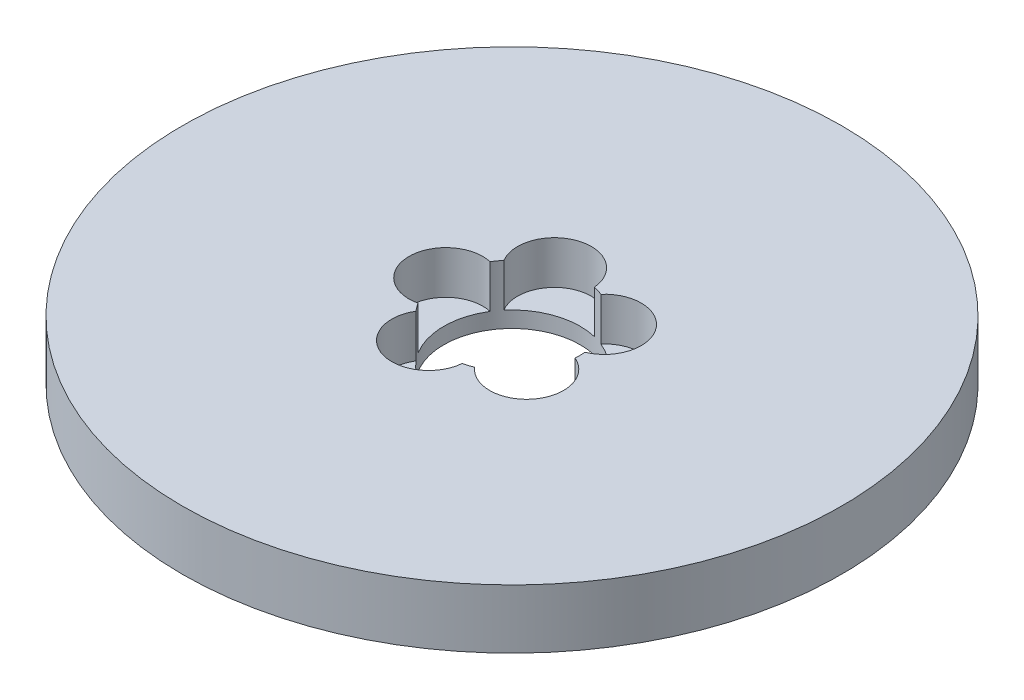
SolidWorks part; units mm, degrees
ref_plane "Front Plane" through (0, 0, 0) normal (0, 0, 1) x (1, 0, 0)
ref_plane "Top Plane" through (0, 0, 0) normal (0, 1, 0) x (1, 0, 0)
ref_plane "Right Plane" through (0, 0, 0) normal (1, 0, 0) x (0, 0, -1)
sketch "Sketch1" plane through (0, 0, 0) normal (0, 1, 0) x (1, 0, 0)
  circle A0 centre (0, 0) radius 72.5
  dimension "FLANGE_OD" = 145
extrude "Boss-Extrude1" add sketch "Sketch1" along normal blind 13
sketch "Sketch2" plane through (0, 0, 0) normal (0, 1, 0) x (1, 0, 0)
  circle A0 centre (0, 0) radius 15
  dimension "BORE_D" = 30
extrude "Cut-Extrude1" cut sketch "Sketch2" along normal through all
sketch "Sketch3" plane through (0, 13, 0) normal (0, 1, 0) x (1, 0, 0)
  circle A0 centre (0, 0) radius 14.5451 construction
  circle A1 centre (-14.5451, 0) radius 8.1185
  dimension "BOLT_D" = 16.237
  dimension "BOLT_PCD" = 29.0903
extrude "Cut-Extrude2" cut sketch "Sketch3" against normal blind 9.474
pattern_circular "CirPattern1" count 5 over 360 about axis through (0, 0, 0) along (0, 1, 0) of "Cut-Extrude2"
